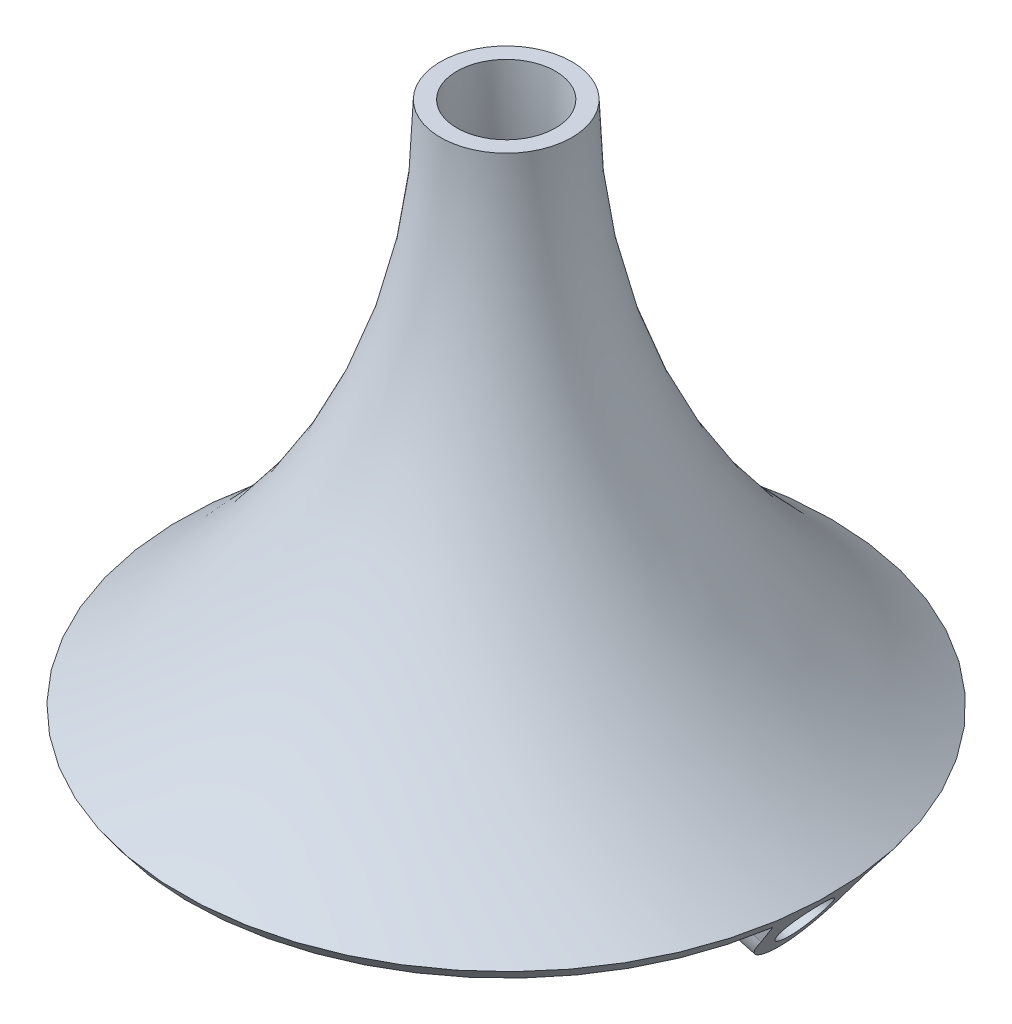
SolidWorks part; units mm, degrees
ref_plane "Front Plane" through (0, 0, 0) normal (0, 0, 1) x (1, 0, 0)
ref_plane "Top Plane" through (0, 0, 0) normal (0, 1, 0) x (1, 0, 0)
ref_plane "Right Plane" through (0, 0, 0) normal (1, 0, 0) x (0, 0, -1)
sketch "Sketch1" plane through (0, 0, 0) normal (0, 0, 1) x (1, 0, 0)
  line L0 (0, 0) -> (0, 71027.4494) construction
  line L1 (12.7, 83.1835) -> (12.7, 30.536) construction
  line L2 (63.5, -18.4165) -> (61.595, -20.9565)
  line L3 (12.7, 83.1835) -> (9.525, 83.1835)
  arc A0 (12.7, 83.1835) -> (63.5, -18.4165) centre (139.7, 83.1835) ccw
  arc A1 (9.525, 83.1835) -> (61.595, -20.9565) centre (139.7, 83.1835) ccw
  dimension "D1" = 12.7
  dimension "D2" = 101.6
  dimension "D3" = 63.5
  dimension "D4" = 3.175
revolve "Revolve1" add sketch "Sketch1" angle 360 about L0
sketch "Sketch2" plane through (0, 0, 0) normal (0, 0, 1) x (1, 0, 0)
  line L0 (49.1455, -22.9192) -> (63.5318, -26.774) construction
  line L1 (50.411, -18.1963) -> (51.2327, -15.1295)
  line L2 (51.2327, -15.1295) -> (63.5, -18.4165)
  line L3 (63.5, -18.4165) -> (62.6782, -21.4833)
  line L4 (62.6782, -21.4833) -> (50.411, -18.1963)
  line L5 (0, 0) -> (12.6434, 0) construction
  dimension "D1" = 15
  dimension "D2" = 3.175
  dimension "D3" = 9.779
  dimension "D4" = 12.7
revolve "Revolve2" add sketch "Sketch2" angle 360 about L0
sketch "Sketch3" plane through (63.8504, -17.1087, 0) normal (0.9659, -0.2588, 0) x (0, 0, -1)
  line L1 (-8.0645, -9.4185) -> (8.0645, -9.4185)
  line L2 (-8.0645, -9.4185) -> (-13.0781, 19.0152)
  line L3 (-13.0781, 19.0152) -> (13.0781, 19.0152)
  line L4 (8.0645, -9.4185) -> (13.0781, 19.0152)
  circle A0 centre (0, -9.4185) radius 4.8895
  circle A1 centre (0, -9.4185) radius 8.0645
  circle A2 centre (0, -9.4185) radius 8.0645 construction
  point P8 (0, 19.0152)
  circle M1 centre (0, -9.4185) radius 8.0645
  circle M2 centre (0, -9.4185) radius 4.8895
  dimension "D1" = 80
extrude "Boss-Extrude1" add sketch "Sketch3" against normal blind 19.05 contours L4 L3 L2 M1 | L1 M1 M2 | L1 M1 M2 region at (62.7249, -21.3091, 0) region at (61.3661, -26.3804, -6.477) region at (66.0147, -9.0316, 0)
sketch "Sketch6" plane through (0, 0, 0) normal (0, 0, 1) x (1, 0, 0)
  line L0 (47.6523, -8.8641) -> (51.9603, -33.2958)
  line L2 (88.1923, -58.6958) -> (0, -58.6958)
  line L3 (0, -58.6958) -> (0, 0)
  line L5 (51.9603, -33.2958) -> (62.7923, -18.4165)
  line L6 (12.7, 83.1835) -> (88.1923, 83.1835)
  line L7 (62.7923, -18.4165) -> (-63.5, -18.4165) construction
  line L8 (88.1923, 83.1835) -> (88.1923, -58.6958)
  line L10 (0, 0) -> (39.5699, 0)
  line L11 (46.6179, -7.8179) -> (46.3741, -8.7277) construction
  arc A1 (12.7, 83.1835) -> (62.7923, -18.4165) centre (140.7816, 83.1835) ccw
  arc A2 (12.7, 83.1835) -> (47.5773, -4.2373) centre (139.7, 83.1835) ccw construction
  arc A5 (9.525, 83.1835) -> (46.6179, -7.8179) centre (139.7, 83.1835) ccw construction
  arc A6 (39.5699, 0) -> (47.6523, -8.8641) centre (139.7, 83.1835) ccw
  spline S0 degree 3 poles (62.7923, -18.4165) (60.0717, -16.4229) (57.4191, -14.3257) (53.5395, -11.0281) (52.2607, -9.9016) (49.7477, -7.6099) (48.5142, -6.4454) (47.3024, -5.2632) knots 0 0 0 0 0.5 0.5 0.75 0.75 1 1 1 1 construction
  dimension "D1" = 80
  dimension "D2" = 25.4
  dimension "D3" = 25.4
  dimension "D4" = 1.27
revolve "Cut-Revolve1" cut sketch "Sketch6" angle 360 about L3
pattern_circular "CirPattern1" count 3 every 120 about axis through (0, 0, 0) along (0, 1, 0) of "Revolve2", "Boss-Extrude1", "Cut-Revolve1"
equation "\"Socket Depth\"\t= 1.5in'Depth of Sockets in part"
equation "\"Roof Angle\"\t= 15deg'Angle of spoke to roof"
equation "\"Spoke Diameter\"= .385in'Diameter of spoke"
equation "\"Part Thickness\"= .125in'Thickness of injection-molded walls"
equation "\"Spoke Length\"\t= 8in'Length of spokes"
equation "\"Spoke Length2\"\t= 12in'length of spokes"
equation "\"Spout diameter\"= 1.25in' Diameter of opening for bugs to enter"
equation "\"Trap Depth\"\t= 2in\t'Depth of Trough around trap openings"
equation "\"D4@Sketch1\"=\"Part Thickness\""
equation "\"D1@Sketch2\"=\"Roof Angle\""
equation "\"D2@Sketch2\"=\"Part Thickness\""
equation "\"D3@Sketch2\"=\"Spoke Diameter\""
